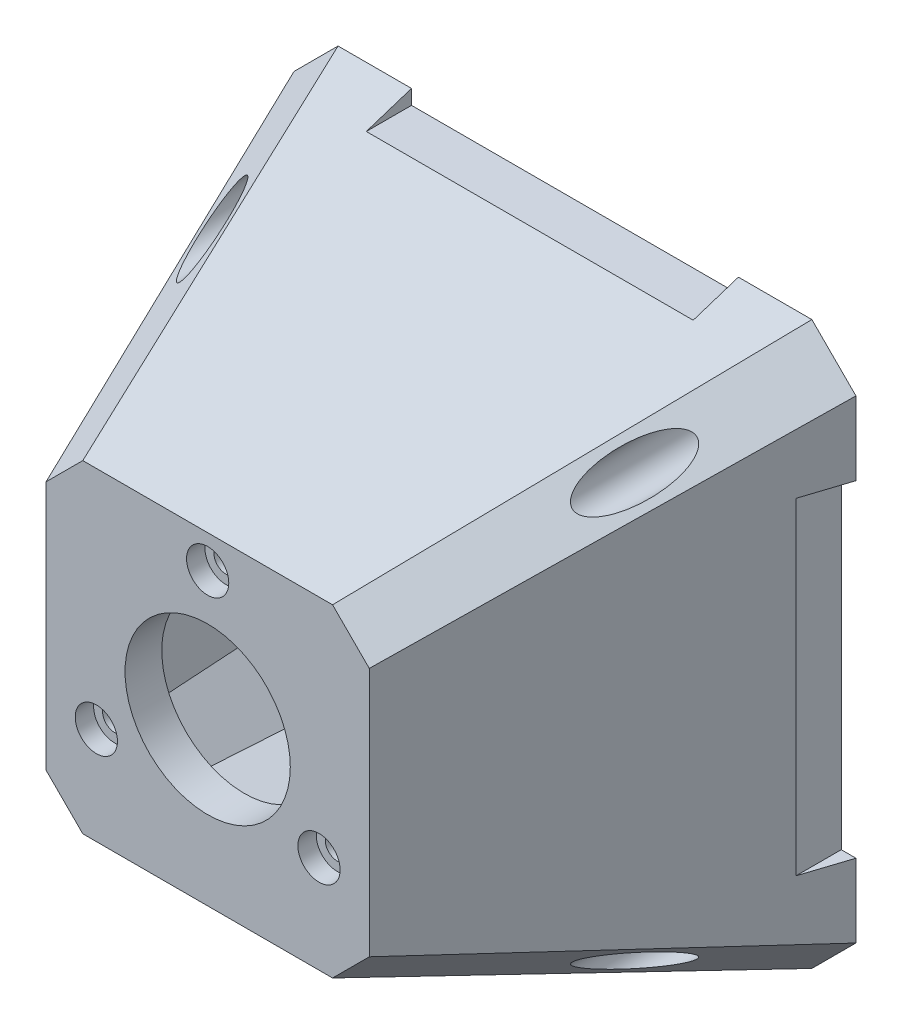
SolidWorks part; units mm, degrees
note: '?' marks a value the reader was unsure of.
ref_plane "Front Plane" through (0, 0, 0) normal (0, 0, 1) x (1, 0, 0)
ref_plane "Top Plane" through (0, 0, 0) normal (0, 1, 0) x (1, 0, 0)
ref_plane "Right Plane" through (0, 0, 0) normal (1, 0, 0) x (0, 0, -1)
sketch "Sketch1" plane through (0, 0, 0) normal (0, 0, 1) x (1, 0, 0)
  line L5 (38.25, 32.25) -> (32.25, 38.25)
  line L10 (0, -42.0203) -> (0, 42.0203) construction
  line L11 (42.0203, 0) -> (-42.0203, 0) construction
  line L33 (38.25, -32.25) -> (32.25, -38.25)
  line L34 (32.25, -38.25) -> (-32.25, -38.25)
  line L35 (38.25, -32.25) -> (38.25, 32.25)
  line L36 (32.25, 38.25) -> (-32.25, 38.25)
  line L37 (-38.25, -32.25) -> (-38.25, 32.25)
  line L38 (38.25, -38.25) -> (-38.25, 38.25) construction
  line L39 (38.25, 38.25) -> (-38.25, -38.25) construction
  line L40 (-32.25, -38.25) -> (-38.25, -32.25)
  line L41 (-32.25, 38.25) -> (-38.25, 32.25)
  circle A0 centre (-28.75, 28.75) radius 1.65 construction
  circle A1 centre (28.75, 28.75) radius 1.65 construction
  circle A2 centre (28.75, -28.75) radius 1.65 construction
  circle A3 centre (-28.75, -28.75) radius 1.65 construction
  point P0 (0, 0)
  point P1 (-34.8473, -26.1137)
  point P2 (0, 0)
  point P6 (-33.1619, 33.1619)
  point P13 (0, 0)
  point P27 (0, 0)
  point P45 (0, 0)
  dimension "D2" = 3.3
  dimension "D3" = 76.5
  dimension "D4" = 76.5
  dimension "D5" = 9.5
ref_plane "Plane1" through (0, 0, 50) normal (0, 0, 1) x (1, 0, 0)
sketch "Sketch2" plane through (0, 0, 50) normal (0, 0, 1) x (1, 0, 0)
  line L1 (-17, -22) -> (17, -22)
  line L2 (-22, -17) -> (-22, 17)
  line L3 (-17, 22) -> (17, 22)
  line L4 (22, -17) -> (22, 17)
  line L5 (-22, -22) -> (22, 22) construction
  line L6 (-22, 22) -> (22, -22) construction
  line L7 (0, -55) -> (0, 55) construction
  line L8 (-22, 17) -> (-17, 22)
  line L9 (17, 22) -> (22, 17)
  line L10 (17, -22) -> (22, -17)
  line L11 (-22, -17) -> (-17, -22)
  circle A0 centre (0, 0) radius 22 construction
  circle A1 centre (0, 17.5) radius 2.6 construction
  circle A2 centre (0, 0) radius 17.5 construction
  circle A3 centre (15.1554, -8.75) radius 2.6 construction
  circle A4 centre (-15.1554, -8.75) radius 2.6 construction
  circle A5 centre (0, 0) radius 11 construction
  point P0 (0, 0)
  point P21 (0, 0)
  point P29 (0, 0)
  dimension "D2" = 44
  dimension "D3" = 5.2
  dimension "D4" = 35
  dimension "D6" = 22
  dimension "D1" = 44
  dimension "D5" = 3
loft "Loft2" add profiles "Sketch2", "Sketch1"
sketch "Sketch3" plane through (0, 0, 0) normal (0, 0, -1) x (-1, 0, 0)
  line L2 (0, 55) -> (0, -55) construction
  line L3 (55, 0) -> (-55, 0) construction
  line L4 (-32.25, 38.25) -> (32.25, 38.25) construction
  line L5 (-38.25, -32.25) -> (-38.25, 32.25) construction
  circle A0 centre (-28.75, 28.75) radius 1.65
  circle A1 centre (28.75, 28.75) radius 1.65
  circle A2 centre (28.75, -28.75) radius 1.65
  circle A3 centre (-28.75, -28.75) radius 1.65
  dimension "D1" = 3.3
  dimension "D2" = 9.5
  dimension "D3" = 9.5
extrude "Cut-Extrude1" cut sketch "Sketch3" against normal blind 50
sketch "Sketch4" plane through (0, 0, 50) normal (0, 0, 1) x (1, 0, 0)
  line L0 (0, -55) -> (0, 55) construction
  line L1 (55, 0) -> (-55, 0) construction
  circle A0 centre (-28.75, 28.75) radius 2.875
  circle A1 centre (28.75, 28.75) radius 2.875
  circle A2 centre (28.75, -28.75) radius 2.875
  circle A3 centre (-28.75, -28.75) radius 2.875
  dimension "D1" = 5.75
extrude "Cut-Extrude2" cut sketch "Sketch4" against normal offset from surface (47.5 mm away) 2.5 up to face at (30.4, -28.75, 0)
sketch "Sketch5" plane through (0, 0, 50) normal (0, 0, 1) x (1, 0, 0)
  circle A0 centre (0, 0) radius 11.25
  dimension "D1" = 22.5
extrude "Cut-Extrude3" cut sketch "Sketch5" against normal through all
sketch "Sketch6" plane through (0, 0, 0) normal (0, 0, -1) x (-1, 0, 0)
  line L1 (-22.25, 38.25) -> (22.25, 38.25)
  line L2 (-22.25, 38.25) -> (-22.25, 36.25)
  line L3 (-22.25, 36.25) -> (22.25, 36.25)
  line L4 (22.25, 38.25) -> (22.25, 36.25)
  line L16 (-32.25, 38.25) -> (32.25, 38.25) construction
  line L17 (38.25, 22.25) -> (36.25, 22.25)
  line L18 (38.25, 22.25) -> (38.25, -22.25)
  line L19 (38.25, -22.25) -> (36.25, -22.25)
  line L20 (36.25, 22.25) -> (36.25, -22.25)
  line L21 (22.25, -38.25) -> (22.25, -36.25)
  line L22 (22.25, -38.25) -> (-22.25, -38.25)
  line L23 (-22.25, -38.25) -> (-22.25, -36.25)
  line L24 (22.25, -36.25) -> (-22.25, -36.25)
  line L25 (-38.25, -22.25) -> (-36.25, -22.25)
  line L26 (-38.25, -22.25) -> (-38.25, 22.25)
  line L27 (-38.25, 22.25) -> (-36.25, 22.25)
  line L28 (-36.25, -22.25) -> (-36.25, 22.25)
  point P21 (0, 0)
  dimension "D1" = 2
  dimension "D3" = 10
  dimension "D4" = 10
  dimension "D2" = 4
extrude "Cut-Extrude4" cut sketch "Sketch6" against normal up to next
sketch "Sketch7" plane through (0, 0, 0) normal (0, 0, -1) x (-1, 0, 0)
  line L6 (0, 27.5001) -> (0, -27.5001) construction
  line L7 (27.5001, 0) -> (-27.5001, 0) construction
  line L10 (18.864, -26.5) -> (26.5, -18.864)
  line L13 (26.5, -18.864) -> (26.5, 18.864)
  line L49 (26.5, 18.864) -> (18.864, 26.5)
  line L50 (18.864, 26.5) -> (-18.864, 26.5)
  line L51 (-18.864, 26.5) -> (-26.5, 18.864)
  line L52 (-26.5, 18.864) -> (-26.5, -18.864)
  line L53 (-26.5, -18.864) -> (-18.864, -26.5)
  line L54 (-18.864, -26.5) -> (18.864, -26.5)
  point P9 (0, 26.5)
  point P12 (26.5, 0)
  dimension "D1" = 53
  dimension "D3" = 7.636
  dimension "D4" = 7.636
ref_plane "Plane2" through (0, 0, 45) normal (0, 0, 1) x (1, 0, 0)
sketch "Sketch8" plane through (0, 0, 45) normal (0, 0, 1) x (1, 0, 0)
  line L92 (22, -17) -> (22, 17)
  line L93 (17, -22) -> (22, -17)
  line L94 (-17, -22) -> (17, -22)
  line L95 (-22, -17) -> (-17, -22)
  line L96 (-22, 17) -> (-22, -17)
  line L97 (-17, 22) -> (-22, 17)
  line L98 (17, 22) -> (-17, 22)
  line L99 (22, 17) -> (17, 22)
  line L100 (22, -17) -> (22, 17)
  line L101 (17, -22) -> (22, -17)
  line L102 (-17, -22) -> (17, -22)
  line L103 (-22, -17) -> (-17, -22)
  line L104 (-22, 17) -> (-22, -17)
  line L105 (-17, 22) -> (-22, 17)
  line L106 (17, 22) -> (-17, 22)
  line L107 (22, 17) -> (17, 22)
  dimension "D1" = 4.5
loft "Cut-Loft2" cut profiles "Sketch8", "Sketch7"
sketch "Sketch9" plane through (0, 0, 50) normal (0, 0, 1) x (1, 0, 0)
  line L0 (0, -27.5001) -> (0, 27.5001) construction
  circle A0 centre (0, 17.5) radius 1.65
  circle A1 centre (0, 0) radius 17.5 construction
  circle A2 centre (15.1554, -8.75) radius 1.65
  circle A3 centre (-15.1554, -8.75) radius 1.65
  point P13 (0, 0)
  dimension "D1" = 35
  dimension "D2" = 3.3
  dimension "D3" = 3
extrude "Cut-Extrude6" cut sketch "Sketch9" against normal up to next
sketch "Sketch11" plane through (0, 0, 45) normal (0, 0, -1) x (-1, 0, 0)
  circle A0 centre (0, 0) radius 22.5
  dimension "D1" = 45
extrude "Cut-Extrude8" cut sketch "Sketch11" along normal up to next
sketch "Sketch12" plane through (0, 0, 45) normal (0, 0, -1) x (-1, 0, 0)
  line L0 (-22, 4.717) -> (-22, 17)
  line L3 (-22, 17) -> (-17, 22)
  line L4 (-17, 22) -> (-4.717, 22)
  line L7 (17, 22) -> (22, 17)
  line L8 (22, 17) -> (22, 4.717)
  line L9 (22, -17) -> (17, -22)
  line L10 (17, -22) -> (4.717, -22)
  line L11 (-17, -22) -> (-22, -17)
  line L14 (-22, -17) -> (-22, -4.717)
  line L15 (4.717, 22) -> (17, 22)
  line L16 (22, -4.717) -> (22, -17)
  line L17 (-4.717, -22) -> (-17, -22)
  line L18 (-22, 4.717) -> (-22, 17) construction
  line L19 (-22, 17) -> (-17, 22) construction
  arc A0 (-22, -4.717) -> (-4.717, -22) centre (0, 0) ccw
  arc A1 (-4.717, 22) -> (-22, 4.717) centre (0, 0) ccw
  arc A2 (22, 4.717) -> (4.717, 22) centre (0, 0) ccw
  arc A3 (4.717, -22) -> (22, -4.717) centre (0, 0) ccw
  point P5 (17, -22)
  point P6 (-22, 17)
  point P9 (0, 0)
  point P12 (22, -17)
  point P14 (0, 0)
  point P15 (0, 0)
  point P16 (0, 0)
  point P17 (0, 0)
  point P19 (22, 17)
  point P21 (17, 22)
  point P27 (-22, -17)
  point P28 (-17, -21.932)
  point P29 (0, 0)
  point P36 (0, 0)
  point P37 (-22, 9.2652)
  point P38 (-22, 7.5668)
  point P40 (0, 0)
  point P41 (-17, 22)
  point P44 (0, 0)
  point P45 (0, 0)
extrude "Boss-Extrude2" add sketch "Sketch12" along normal blind 4.9
sketch "Sketch13" plane through (0, 0, 50) normal (0, 0, 1) x (1, 0, 0)
  circle A0 centre (0, 17.5) radius 2.875
  dimension "D1" = 5.75
extrude "Cut-Extrude9" cut sketch "Sketch13" against normal blind 2.5
ref_axis "Axis1" through (0, 0, 52.5001) along (0, 0, -1)?
pattern_circular "CirPattern1" count 3 over 360 about axis through (0, 0, 0) along (0, 0, 1) of "Cut-Extrude9"
